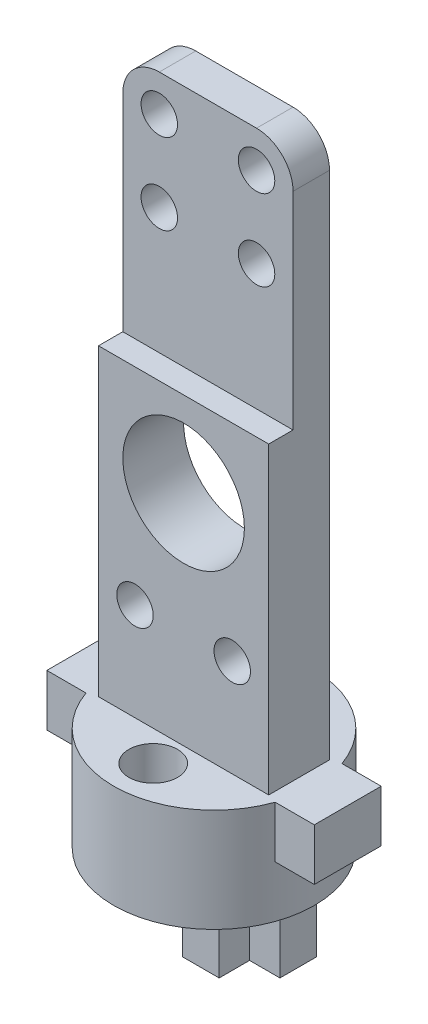
SolidWorks part; units mm, degrees
ref_plane "Plan de face" through (0, 0, 0) normal (0, 0, 1) x (1, 0, 0)
ref_plane "Plan de dessus" through (0, 0, 0) normal (0, 1, 0) x (1, 0, 0)
ref_plane "Plan de droite" through (0, 0, 0) normal (1, 0, 0) x (0, 0, -1)
sketch "Esquisse1" plane through (0, 0, 0) normal (0, 1, 0) x (1, 0, 0)
  line L1 (-11, 2.75) -> (11, 2.75)
  line L2 (-11, 2.75) -> (-11, -2.75)
  line L3 (-11, -2.75) -> (11, -2.75)
  line L4 (11, 2.75) -> (11, -2.75)
  circle A0 centre (0, 0) radius 8.25
  dimension "D1" = 16.5
  dimension "D2" = 5.5
  dimension "D3" = 2.75
  dimension "D4" = 22
  dimension "D5" = 11
extrude "Boss.-Extru.1" add sketch "Esquisse1" along normal mid plane 8.5 contours L3 A0 | L3 A0 L1 | L1 A0 region at (0, 0, -5.0282) region at (0, 0, 0) region at (0, 0, 5.0282)
extrude "Boss.-Extru.2" add sketch "Esquisse1<3>" along normal blind 4.25 contours A0 L1 L2 L3 | A0 L3 L4 L1 region at (-9.5439, 0, 0) region at (9.5439, 0, 0)
sketch "Esquisse1<3>" plane through (0, 0, 0) normal (0, 1, 0) x (1, 0, 0) same geometry as "Esquisse1"
sketch "Esquisse2" plane through (0, 4.25, 0) normal (0, 1, 0) x (1, 0, 0)
  circle A0 centre (0, -5) radius 2
  dimension "D1" = 4
  dimension "D2" = 5
extrude "Enlèv. mat.-Extru.1" cut sketch "Esquisse2" against normal up to surface (8.5 mm away)
sketch "Esquisse3" plane through (0, -4.25, 0) normal (0, -1, 0) x (1, 0, 0)
  line L1 (-4, -1.4248) -> (4, -1.4248)
  line L2 (-4, -1.4248) -> (-4, -4.4248)
  line L3 (-4, -4.4248) -> (4, -4.4248)
  line L4 (4, -1.4248) -> (4, -4.4248)
  line L5 (-1.5, 1.0752) -> (1.5, 1.0752)
  line L6 (-1.5, 1.0752) -> (-1.5, -6.9248)
  line L7 (-1.5, -6.9248) -> (1.5, -6.9248)
  line L8 (1.5, 1.0752) -> (1.5, -6.9248)
  dimension "D1" = 1.5
  dimension "D2" = 3
  dimension "D3" = 3
  dimension "D4" = 8
  dimension "D5" = 2.5
  dimension "D6" = 2.5
  dimension "D7" = 8
extrude "Boss.-Extru.3" add sketch "Esquisse3" along normal blind 8 contours L6 L1 L2 L3 | L8 L5 L6 L1 | L8 L1 L6 L3 | L8 L3 L6 L7 | L1 L8 L3 L4 region at (-2.75, -4.25, -2.9248) region at (0, -4.25, -0.1748) region at (0, -4.25, -2.9248) region at (2.75, -4.25, -2.9248) region at (0, -4.25, -5.6748)
sketch "Esquisse4" plane through (0, 4.25, 0) normal (0, 1, 0) x (1, 0, 0)
  line L1 (-7, 2.5) -> (7, 2.5)
  line L2 (-7, 2.5) -> (-7, -2.5)
  line L3 (-7, -2.5) -> (7, -2.5)
  line L4 (7, 2.5) -> (7, -2.5)
  dimension "D1" = 5
  dimension "D2" = 2.5
  dimension "D3" = 14
  dimension "D4" = 7
extrude "Boss.-Extru.4" add sketch "Esquisse4" along normal blind 45
sketch "Esquisse5" plane through (0, 0, 2.5) normal (0, 0, 1) x (1, 0, 0)
  line L0 (-7, 49.25) -> (-7, 4.25) construction
  line L2 (-7, 49.25) -> (7, 49.25) construction
  line L3 (7, 49.25) -> (7, 4.25) construction
  circle A0 centre (-4, 46.25) radius 1.5
  circle A1 centre (4, 46.25) radius 1.5
  circle A2 centre (-4, 39.6036) radius 1.5
  circle A3 centre (4, 39.6036) radius 1.5
  circle A4 centre (0, 22.25) radius 5
  circle A5 centre (-4, 12.2788) radius 1.5
  circle A6 centre (4, 12.2788) radius 1.5
  dimension "D1" = 10
  dimension "D2" = 3
  dimension "D3" = 3
  dimension "D4" = 3
  dimension "D5" = 3
  dimension "D6" = 3
  dimension "D7" = 3
  dimension "D8" = 3
  dimension "D9" = 3
  dimension "D10" = 3
  dimension "D11" = 3
  dimension "D12" = 3
  dimension "D13" = 3
  dimension "D14" = 3
  dimension "D15" = 3
  dimension "D16" = 27
extrude "Enlèv. mat.-Extru.2" cut sketch "Esquisse5" against normal up to surface (5 mm away) up to face at (0, 26.75, -2.5)
fillet "Congé1" radius 3 2 edges at (7, 49.25, 0) (-7, 49.25, 0)
sketch "Esquisse6" plane through (7, 0, 0) normal (1, 0, 0) x (0, 0, -1)
  line L2 (-2.5, 49.25) -> (-0.5, 49.25)
  line L3 (-2.5, 49.25) -> (-2.5, 29.25)
  line L4 (-2.5, 29.25) -> (-0.5, 29.25)
  line L8 (-0.5, 49.25) -> (-0.5, 29.25)
  dimension "D1" = 20
  dimension "D2" = 2
extrude "Enlèv. mat.-Extru.4" cut sketch "Esquisse6" against normal up to surface (14 mm away) up to face at (-7, 25.25, 0)
